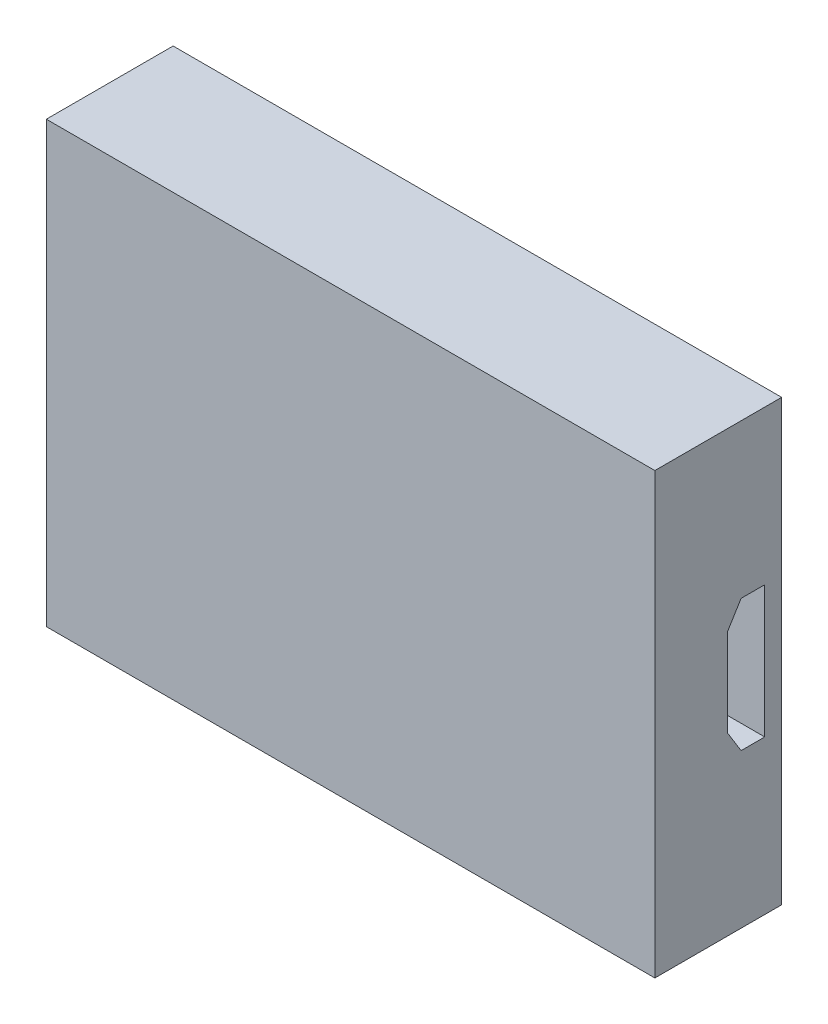
SolidWorks part; units mm, degrees
note: The reader was unsure of these and kept them because the rebuilt part matched: shared geometry of "Sketch1<4>".
ref_plane "Front Plane" through (0, 0, 0) normal (0, 0, 1) x (1, 0, 0)
ref_plane "Top Plane" through (0, 0, 0) normal (0, 1, 0) x (1, 0, 0)
ref_plane "Right Plane" through (0, 0, 0) normal (1, 0, 0) x (0, 0, -1)
sketch "Sketch1" plane through (0, 0, 0) normal (0, 0, 1) x (1, 0, 0)
  line L0 (13.75, 8.6) -> (13.75, -8.6) construction
  line L1 (13.75, 10) -> (-16.25, 10)
  line L2 (13.75, 10) -> (13.75, -10)
  line L3 (13.75, -10) -> (-16.25, -10)
  line L4 (-16.25, 10) -> (-16.25, -10)
  line L5 (13.75, 10) -> (-16.25, -10) construction
  line L6 (13.75, -10) -> (-16.25, 10) construction
  line L7 (16.75, 13) -> (16.75, -13)
  line L8 (16.75, -13) -> (-19.25, -13)
  line L9 (-19.25, 13) -> (-19.25, -13)
  line L10 (16.75, 13) -> (-19.25, 13)
  point P0 (0, 0)
  point P6 (15, -10.8841)
  point P7 (0, 0)
  point P8 (0, 0)
  dimension "D1" = 30
  dimension "D2" = 20
  dimension "D3" = 3
extrude "Extrude-Thin1" add sketch "Sketch1" against normal blind 5.5 thin contours L1 L4 L3 L2
sketch "Sketch2" plane through (16.75, 0, 0) normal (1, 0, 0) x (0, 0, -1)
  line L0 (0, 13) -> (0, -13) construction
  line L5 (0, 0) -> (7, 0) construction
  line L6 (4.5, -3.9) -> (4.5, 3.9)
  line L7 (4.5, -3.9) -> (3.1, -3.9)
  line L8 (3.1, -3.9) -> (2.3, -2.6)
  line L9 (2.3, -2.6) -> (2.3, 0)
  line L10 (7, -13) -> (7, 13) construction
  line L11 (2.3, 2.6) -> (2.3, 0)
  line L12 (3.1, 3.9) -> (2.3, 2.6)
  line L13 (4.5, 3.9) -> (3.1, 3.9)
  point P1 (2.3, -1.3)
  point P7 (2.3, 1.3)
  point P14 (4.5, 0)
  dimension "D1" = 3.9
  dimension "D2" = 2.2
  dimension "D3" = 1.4
  dimension "D4" = 1.3
  dimension "D5" = 2.3
extrude "Cut-Extrude1" cut sketch "Sketch2" against normal up to next
extrude "Boss-Extrude3" add sketch "Sketch1<4>" along normal blind 2 contours L1 L4 L3 L2 | L7 L10 L9 L8 L4 L1 L2 L3
sketch "Sketch1<4>" plane through (0, 0, 0) normal (0, 0, 1) x (1, 0, 0) same geometry as "Sketch1"
sketch "Sketch4" plane through (0, 0, -5.5) normal (0, 0, -1) x (-1, 0, 0)
  line L0 (-16.75, 13) -> (19.25, 13) construction
  line L1 (-16.75, 13) -> (-16.75, -13) construction
  line L2 (-14.75, 11) -> (17.25, 11) construction
  circle A0 centre (-14.75, 11) radius 1.25
  circle A1 centre (17.25, 11) radius 1.25
  circle A2 centre (17.25, -11) radius 1.25
  circle A3 centre (-14.75, -11) radius 1.25
  dimension "D1" = 2.5
  dimension "D2" = 2
  dimension "D3" = 2
  dimension "D6" = 32
  dimension "D4" = 2
  dimension "D5" = 2
extrude "Cut-Extrude4" cut sketch "Sketch4" against normal blind 5
sketch "Sketch5" plane through (-19.25, 0, 0) normal (-1, 0, 0) x (0, 0, 1)
  line L1 (-5.5, 0) -> (2, 0) construction
  line L2 (-5.5, 13) -> (-5.5, -13) construction
  line L3 (2, 13) -> (2, -13) construction
  circle A0 centre (-2.5, 4.2) radius 0.5
  circle A1 centre (-2.5, -4.2) radius 0.5
  dimension "D1" = 4.2
  dimension "D2" = 1
  dimension "D3" = 4.5
extrude "Cut-Extrude5" cut sketch "Sketch5" against normal up to next
